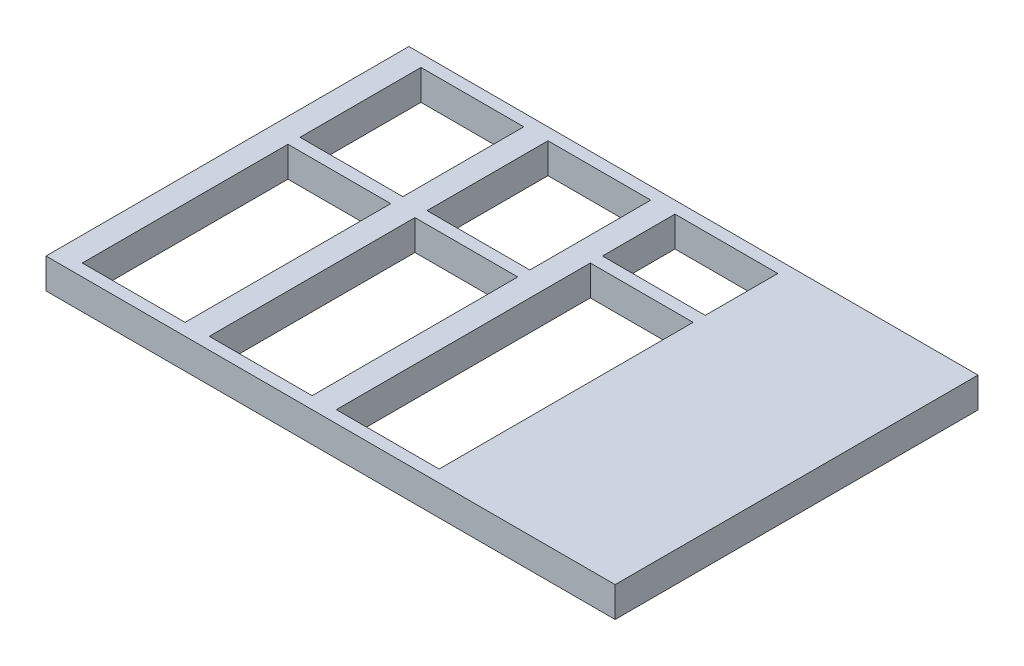
SolidWorks part; units mm, degrees
ref_plane "Front" through (0, 0, 0) normal (0, 0, 1) x (1, 0, 0)
ref_plane "Top" through (0, 0, 0) normal (0, 1, 0) x (1, 0, 0)
ref_plane "Right" through (0, 0, 0) normal (1, 0, 0) x (0, 0, -1)
sketch "Sketch1" plane through (0, 0, 0) normal (0, 1, 0) x (1, 0, 0)
  line L1 (-47.05, -30) -> (47.05, -30)
  line L2 (-47.05, -30) -> (-47.05, 30)
  line L3 (-47.05, 30) -> (47.05, 30)
  line L4 (47.05, -30) -> (47.05, 30)
  line L5 (-47.05, -30) -> (47.05, 30) construction
  line L6 (-47.05, 30) -> (47.05, -30) construction
  line L7 (-43.05, -28) -> (-26.05, -28)
  line L8 (-43.05, -28) -> (-43.05, 6)
  line L9 (-43.05, 6) -> (-26.05, 6)
  line L10 (-26.05, -28) -> (-26.05, 6)
  line L11 (-43.05, -28) -> (-26.05, 6) construction
  line L12 (-43.05, 6) -> (-26.05, -28) construction
  line L13 (-43.05, 8) -> (-26.05, 8)
  line L14 (-43.05, 8) -> (-43.05, 28)
  line L15 (-43.05, 28) -> (-26.05, 28)
  line L16 (-26.05, 8) -> (-26.05, 28)
  line L17 (-43.05, 8) -> (-26.05, 28) construction
  line L18 (-43.05, 28) -> (-26.05, 8) construction
  line L19 (-5.05, -28) -> (-22.05, -28)
  line L20 (-5.05, -28) -> (-5.05, 6)
  line L21 (-5.05, 6) -> (-22.05, 6)
  line L22 (-22.05, -28) -> (-22.05, 6)
  line L23 (-5.05, -28) -> (-22.05, 6) construction
  line L24 (-5.05, 6) -> (-22.05, -28) construction
  line L25 (-5.05, 28) -> (-22.05, 28)
  line L26 (-5.05, 28) -> (-5.05, 8)
  line L27 (-5.05, 8) -> (-22.05, 8)
  line L28 (-22.05, 28) -> (-22.05, 8)
  line L29 (-5.05, 28) -> (-22.05, 8) construction
  line L30 (-5.05, 8) -> (-22.05, 28) construction
  line L31 (-1.05, -28) -> (15.95, -28)
  line L32 (-1.05, -28) -> (-1.05, 14)
  line L33 (-1.05, 14) -> (15.95, 14)
  line L34 (15.95, -28) -> (15.95, 14)
  line L35 (-1.05, -28) -> (15.95, 14) construction
  line L36 (-1.05, 14) -> (15.95, -28) construction
  line L37 (-1.05, 16) -> (15.95, 16)
  line L38 (-1.05, 16) -> (-1.05, 28)
  line L39 (-1.05, 28) -> (15.95, 28)
  line L40 (15.95, 16) -> (15.95, 28)
  line L41 (-1.05, 16) -> (15.95, 28) construction
  line L42 (-1.05, 28) -> (15.95, 16) construction
  point P0 (0, 0)
  point P6 (-34.55, -11)
  point P11 (-34.55, 18)
  point P16 (-13.55, -11)
  point P21 (-13.55, 18)
  point P26 (7.45, -7)
  point P31 (7.45, 22)
  dimension "D1" = 94.1
  dimension "D2" = 60
  dimension "D3" = 4
  dimension "D4" = 2
  dimension "D5" = 17
  dimension "D6" = 4
  dimension "D7" = 17
  dimension "D8" = 2
  dimension "D9" = 4
  dimension "D10" = 2
  dimension "D11" = 17
  dimension "D12" = 4
  dimension "D13" = 17
  dimension "D14" = 4
  dimension "D15" = 17
  dimension "D16" = 4
  dimension "D17" = 17
  dimension "D18" = 2
  dimension "D19" = 2
  dimension "D20" = 34
  dimension "D21" = 20
  dimension "D22" = 20
  dimension "D23" = 34
  dimension "D24" = 42
  dimension "D25" = 12
extrude "Boss-Extrude1" add sketch "Sketch1" along normal blind 5
